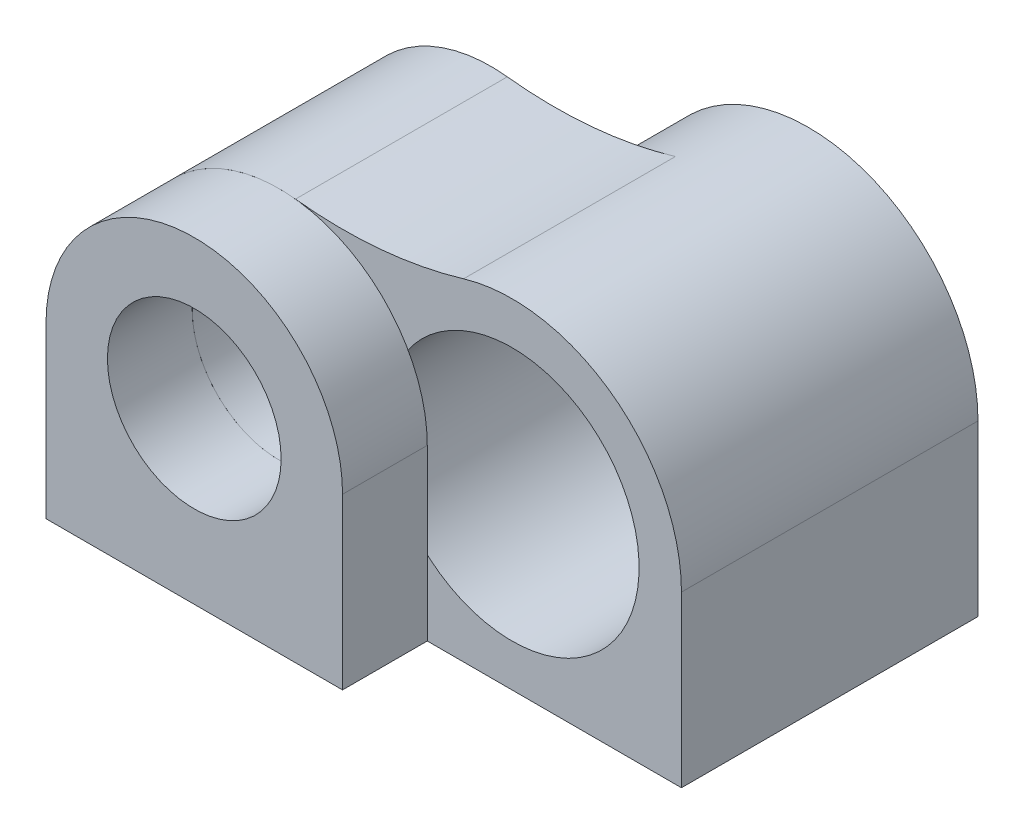
SolidWorks part; units mm, degrees
ref_plane "Front Plane" through (0, 0, 0) normal (0, 0, 1) x (1, 0, 0)
ref_plane "Top Plane" through (0, 0, 0) normal (0, 1, 0) x (1, 0, 0)
ref_plane "Right Plane" through (0, 0, 0) normal (1, 0, 0) x (0, 0, -1)
sketch "Sketch1" plane through (0, 0, 0) normal (0, 0, 1) x (1, 0, 0)
  line L0 (-4, 0) -> (-4, -4)
  line L1 (-4, -4) -> (4, -4)
  line L2 (4, -4) -> (4, 0)
  circle A2 centre (0, 0) radius 3
  arc A3 (4, 0) -> (-4, 0) centre (0, 0) ccw
  dimension "D1" = 6
  dimension "D2" = 8
  dimension "D3" = 4
extrude "Boss-Extrude1" add sketch "Sketch1" along normal blind 7
sketch "Sketch2" plane through (0, 0, 7) normal (0, 0, 1) x (1, 0, 0)
  line L0 (-9, 0) -> (-9, -4)
  line L1 (-2, 0) -> (-2, -4)
  line L2 (-4, -4) -> (4, -4) construction
  line L3 (-2, -4) -> (-9, -4)
  line L4 (-4, 0) -> (-4, -4) construction
  line L5 (-4, 0) -> (-4, -4)
  circle A0 centre (-5.5, 0) radius 2.05
  arc A1 (-2, 0) -> (-9, 0) centre (-5.5, 0) ccw
  arc A2 (4, 0) -> (-4, 0) centre (0, 0) ccw construction
  arc A3 (-3.0909, 2.539) -> (-4, 0) centre (0, 0) ccw
  arc M6 (4, 0) -> (-4, 0) centre (0, 0) ccw
  line M8 (-4, -4) -> (4, -4)
  circle M10 centre (0, 0) radius 3
  dimension "D1" = 4.1
  dimension "D3" = 7
  dimension "D2" = 5.5
  dimension "D4" = 4
extrude "Boss-Extrude6" add sketch "Sketch2" against normal blind 3 contours A1 L0 L3 L5 A0 M6 region at (-6.844, 3.128, 7)
extrude "Boss-Extrude8" add sketch "Sketch2<4>" along normal blind 2 separate body contours A1 L0 L3 L5 A0 M6 | L1 A1 M10 | A0 L5 L1 M8 M10 region at (-6.844, 3.128, 7) region at (-3.106, -1.531, 7) region at (-2.4432, -0.209, 7)
sketch "Sketch2<4>" plane through (0, 0, 7) normal (0, 0, 1) x (1, 0, 0) same geometry as "Sketch2"
extrude "Boss-Extrude9" add sketch "Sketch2<6>" along normal blind 2 from offset 5 contours A1 L0 L3 L5 A0 M6 region at (-6.844, 3.128, 7) offset against normal yes
sketch "Sketch2<6>" plane through (0, 0, 7) normal (0, 0, 1) x (1, 0, 0) same geometry as "Sketch2"
fillet "Fillet2" radius 10 1 edges at (-3.0909, 2.539, 4.5)
extrude "Cut-Extrude5" cut sketch "Sketch2<9>" against normal blind 7 from offset 3 contours A0 offset against normal yes
sketch "Sketch2<9>" plane through (0, 0, 7) normal (0, 0, 1) x (1, 0, 0) same geometry as "Sketch2"
